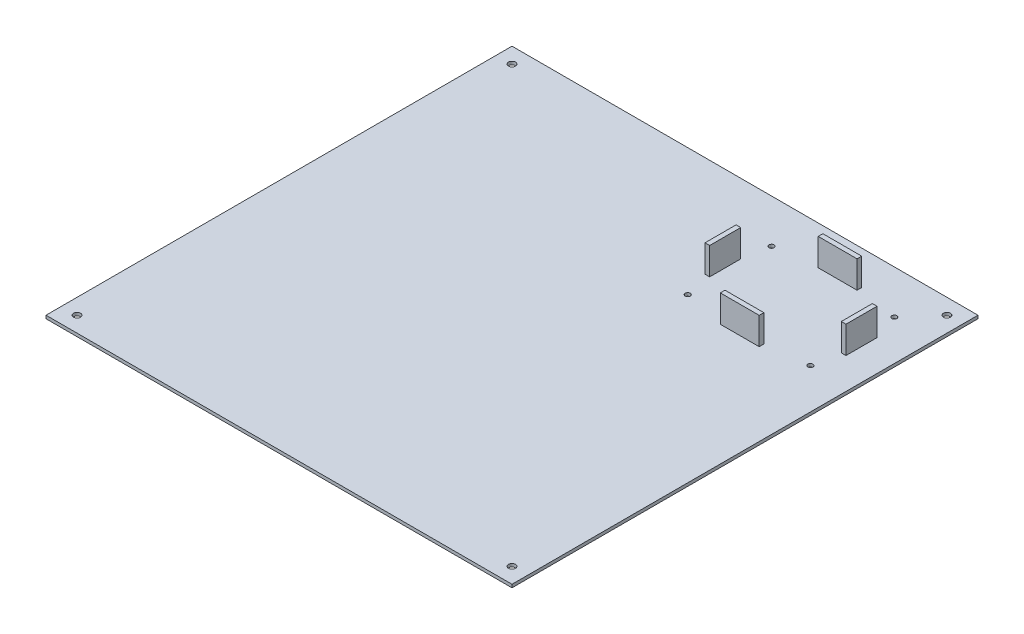
SolidWorks part; units mm, degrees
ref_plane "Front Plane" through (0, 0, 0) normal (0, 0, 1) x (1, 0, 0)
ref_plane "Top Plane" through (0, 0, 0) normal (0, 1, 0) x (1, 0, 0)
ref_plane "Right Plane" through (0, 0, 0) normal (1, 0, 0) x (0, 0, -1)
sketch "Sketch1" plane through (0, 0, 0) normal (0, 1, 0) x (1, 0, 0)
  line L1 (0, 0) -> (600, 0)
  line L2 (0, 0) -> (0, 600)
  line L3 (0, 600) -> (600, 600)
  line L4 (600, 0) -> (600, 600)
  circle A0 centre (20, 580) radius 4.5
  circle A1 centre (580, 580) radius 4.5
  circle A2 centre (580, 20) radius 4.5
  circle A3 centre (20, 20) radius 4.5
  dimension "D3" = 9
  dimension "D1" = 600
  dimension "D2" = 600
  dimension "D4" = 20
  dimension "D5" = 20
  dimension "D8" = 20
  dimension "D9" = 20
  dimension "D6" = 2
  dimension "D7" = 2
extrude "Boss-Extrude1" add sketch "Sketch1" along normal blind 4
sketch "Sketch4" plane through (0, 4, 0) normal (0, 1, 0) x (1, 0, 0)
  line L1 (469.25, 550) -> (469.25, 600) construction
  line L2 (384.5, 550) -> (554, 550) construction
  line L3 (384.5, 550) -> (384.5, 430) construction
  line L4 (384.5, 430) -> (554, 430) construction
  line L5 (554, 550) -> (554, 430) construction
  line L6 (600, 600) -> (0, 600) construction
  line L7 (391.5, 430) -> (391.5, 424) construction
  line L8 (384.5, 437) -> (378.5, 437) construction
  line L9 (547, 550) -> (547, 556) construction
  line L10 (554, 543) -> (560, 543) construction
  line L11 (560, 556) -> (560, 424) construction
  line L12 (560, 424) -> (378.5, 424) construction
  line L13 (378.5, 424) -> (378.5, 556) construction
  line L14 (378.5, 556) -> (560, 556) construction
  line L15 (378.5, 470) -> (378.5, 510)
  line L16 (444.25, 556) -> (494.25, 556)
  line L17 (384.5, 470) -> (384.5, 510)
  line L18 (554, 470) -> (554, 510)
  line L19 (560, 470) -> (560, 510)
  line L20 (444.25, 424) -> (494.25, 424)
  line L21 (444.25, 550) -> (494.25, 550)
  line L22 (444.25, 430) -> (494.25, 430)
  line L23 (378.5, 510) -> (384.5, 510)
  line L24 (384.5, 470) -> (378.5, 470)
  line L25 (444.25, 556) -> (444.25, 550)
  line L26 (494.25, 550) -> (494.25, 556)
  line L27 (554, 510) -> (560, 510)
  line L28 (560, 470) -> (554, 470)
  line L29 (494.25, 430) -> (494.25, 424)
  line L30 (444.25, 424) -> (444.25, 430)
  line L31 (548.25, 544) -> (390.25, 544) construction
  line L32 (469.25, 436) -> (469.25, 544) construction
  line L33 (390.25, 436) -> (548.25, 436) construction
  line L34 (600, 0) -> (600, 600) construction
  circle A0 centre (79.5, 580) radius 4 construction
  circle A1 centre (390.25, 544) radius 3.25
  circle A2 centre (548.25, 544) radius 3.25
  circle A3 centre (390.25, 436) radius 3.25
  circle A4 centre (548.25, 436) radius 3.25
  point P22 (547, 553)
  point P28 (378.5, 490)
  point P31 (469.25, 556)
  point P34 (384.5, 490)
  point P37 (554, 490)
  point P40 (560, 490)
  point P43 (469.25, 424)
  point P46 (469.25, 550)
  point P49 (469.25, 430)
  point P56 (469.25, 490)
  point P58 (469.25, 436)
  point P59 (469.25, 544)
  dimension "D23" = 6.5
  dimension "D24" = 6.5
  dimension "D25" = 6.5
  dimension "D26" = 6.5
  dimension "D1" = 169.5
  dimension "D2" = 120
  dimension "D3" = 50
  dimension "D4" = 40
  dimension "D5" = 6
  dimension "D6" = 6
  dimension "D7" = 6
  dimension "D8" = 6
  dimension "D9" = 6
  dimension "D10" = 13
  dimension "D11" = 13
  dimension "D12" = 13
  dimension "D13" = 13
  dimension "D14" = 40
  dimension "D15" = 50
  dimension "D16" = 50
  dimension "D17" = 40
  dimension "D18" = 158
  dimension "D19" = 5.75
  dimension "D20" = 108
  dimension "D21" = 6
  dimension "D22" = 158
extrude "Cut-Extrude2" cut sketch "Sketch4" against normal up to next contours A1 | A3 | A4 | A2 region at (390.25, 4, -544) region at (548.25, 4, -544) region at (390.25, 4, -436) region at (548.25, 4, -436)
extrude "Boss-Extrude2" add sketch "Sketch4<3>" along normal blind 35 contours L21 L26 L16 L25 | L24 L17 L23 L15 | L28 L19 L27 L18 | L30 L20 L29 L22 region at (381.5, 4, -490) region at (469.25, 4, -553) region at (557, 4, -490) region at (469.25, 4, -427)
sketch "Sketch4<3>" plane through (0, 4, 0) normal (0, 1, 0) x (1, 0, 0) same geometry as "Sketch4"
